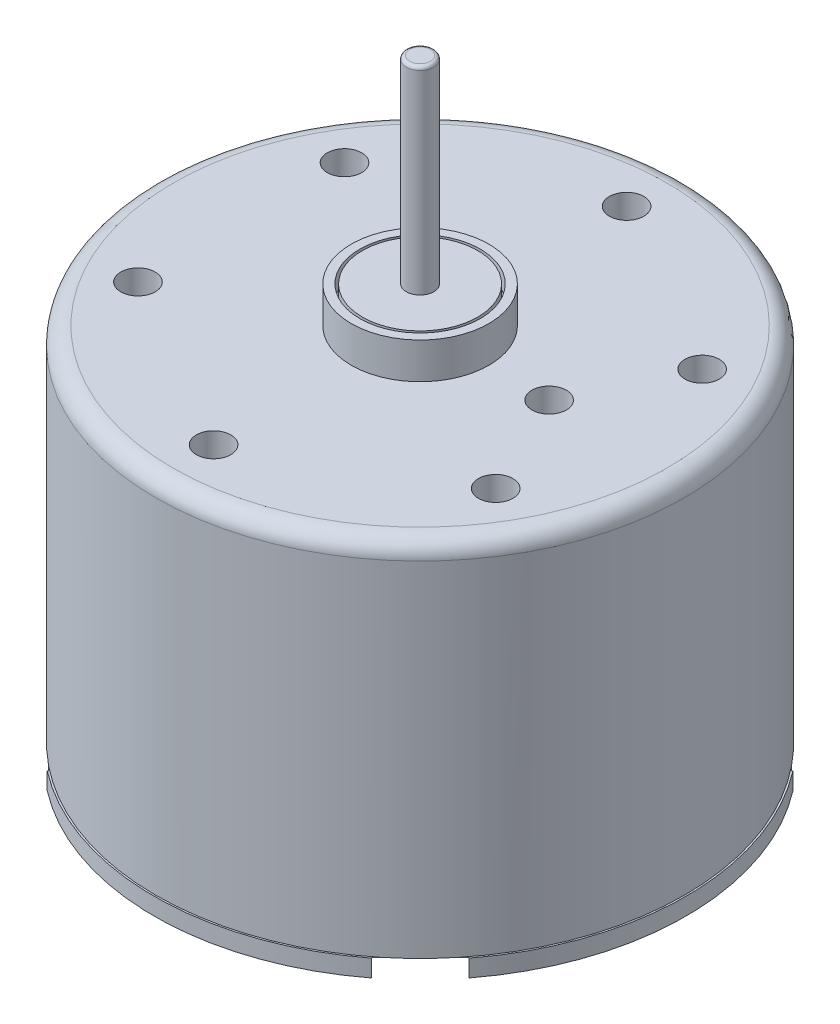
SolidWorks part; units mm, degrees
ref_plane "Plano frontal" through (0, 0, 0) normal (0, 0, 1) x (1, 0, 0)
ref_plane "Plano superior" through (0, 0, 0) normal (0, 1, 0) x (1, 0, 0)
ref_plane "Plano direito" through (0, 0, 0) normal (1, 0, 0) x (0, 0, -1)
sketch "Esboço1" plane through (0, 0, 0) normal (0, 1, 0) x (1, 0, 0)
  circle A0 centre (0, 0) radius 15.35
  dimension "D1" = 30.7
extrude "Ressalto-extrusão1" add sketch "Esboço1" along normal blind 21
sketch "Esboço2" plane through (0, 21, 0) normal (0, 1, 0) x (1, 0, 0)
  circle A0 centre (0, 0) radius 4
  dimension "D1" = 8
extrude "Ressalto-extrusão2" add sketch "Esboço2" along normal blind 2.1
sketch "Esboço3" plane through (0, 23.1, 0) normal (0, 1, 0) x (1, 0, 0)
  circle A0 centre (0, 0) radius 3.35
  circle A1 centre (0, 0) radius 3.5
  dimension "D1" = 6.7
  dimension "D2" = 7
extrude "Corte-extrusão1" cut sketch "Esboço3" against normal blind 1
sketch "Esboço4" plane through (0, 23.1, 0) normal (0, 1, 0) x (1, 0, 0)
  circle A0 centre (0, 0) radius 0.8
  dimension "D1" = 1.6
extrude "Ressalto-extrusão3" add sketch "Esboço4" along normal blind 11.5
fillet "Filete1" radius 0.2 1 edges at (0, 34.6, 0.8)
sketch "Esboço5" plane through (0, 21, 0) normal (0, 1, 0) x (1, 0, 0)
  circle A0 centre (0, 12) radius 1
  circle A1 centre (10.3923, 6) radius 1
  circle A2 centre (10.3923, -6) radius 1
  circle A3 centre (0, -12) radius 1
  circle A4 centre (-10.3923, -6) radius 1
  circle A5 centre (-10.3923, 6) radius 1
  point P16 (0, 0)
  dimension "D1" = 12
  dimension "D2" = 2
  dimension "D3" = 6
extrude "Corte-extrusão2" cut sketch "Esboço5" against normal blind 3
sketch "Esboço6" plane through (0, 21, 0) normal (0, 1, 0) x (1, 0, 0)
  circle A0 centre (7.5, 0) radius 1
  dimension "D1" = 7.5
  dimension "D2" = 2
extrude "Corte-extrusão3" cut sketch "Esboço6" against normal blind 3
fillet "Filete2" radius 1 1 edges at (0, 21, 15.35)
sketch "Esboço7" plane through (0, 0, 0) normal (0, -1, 0) x (1, 0, 0)
  circle A0 centre (0, 0) radius 15.45
  dimension "D1" = 30.9
extrude "Ressalto-extrusão4" add sketch "Esboço7" along normal blind 1
sketch "Esboço8" plane through (0, -1, 0) normal (0, -1, 0) x (1, 0, 0)
  line L0 (-11.2583, 6.5) -> (-5.1962, 3)
  line L1 (0, 13) -> (0, -13) construction
  line L2 (-13, 0) -> (13, 0) construction
  line L3 (11.2583, 6.5) -> (5.1962, 3)
  line L4 (11.2583, -6.5) -> (5.1962, -3)
  line L5 (-11.2583, -6.5) -> (-5.1962, -3)
  arc A0 (-11.2583, -6.5) -> (11.2583, -6.5) centre (0, 0) ccw
  arc A1 (-5.1962, 3) -> (-5.1962, -3) centre (0, 0) ccw
  arc A2 (11.2583, 6.5) -> (-11.2583, 6.5) centre (0, 0) ccw
  arc A3 (5.1962, -3) -> (5.1962, 3) centre (0, 0) ccw
  dimension "D1" = 26
  dimension "D2" = 12
  dimension "D3" = 60
extrude "Corte-extrusão4" cut sketch "Esboço8" against normal blind 1.5
sketch "Esboço9" plane through (0, 0.5, 0) normal (0, -1, 0) x (1, 0, 0)
  circle A0 centre (0, 0) radius 4
  dimension "D1" = 8
extrude "Ressalto-extrusão5" add sketch "Esboço9" along normal blind 2
sketch "Esboço10" plane through (0, 0.5, 0) normal (0, -1, 0) x (1, 0, 0)
  line L0 (-15.45, 0) -> (15.45, 0) construction
  circle A0 centre (-3, 10) radius 3.5
  circle A1 centre (0, 0) radius 15.45 construction
  circle A2 centre (3, -10) radius 3.5
  dimension "D1" = 3
  dimension "D2" = 3
  dimension "D3" = 10
  dimension "D4" = 10
  dimension "D5" = 7
  dimension "D6" = 7
extrude "Corte-extrusão5" cut sketch "Esboço10" against normal blind 3.5 and the other way through all
sketch "Esboço11" plane through (0, 4, 0) normal (0, -1, 0) x (1, 0, 0)
  circle A0 centre (-3, 10) radius 1.25
  circle A1 centre (3, -10) radius 1.25
  circle A3 centre (3, -10) radius 3.5 construction
  dimension "D1" = 2.5
  dimension "D2" = 2.5
  dimension "D3" = 0
  dimension "D4" = 0
extrude "Ressalto-extrusão6" add sketch "Esboço11" along normal blind 4
sketch "Esboço12" plane through (0, -1, 0) normal (0, -1, 0) x (1, 0, 0)
  line L0 (-6.499, -3.0022) -> (-7.1585, -0.0756)
  line L1 (-7.1585, -0.0756) -> (-13.0117, -1.3946)
  line L2 (-13.0117, -1.3946) -> (-12.3522, -4.3212)
  line L3 (-12.3522, -4.3212) -> (-6.499, -3.0022)
  line L4 (0, 0) -> (3.3965, -15.072) construction
  line L5 (13.0117, 1.3946) -> (7.1585, 0.0756)
  line L6 (12.3522, 4.3212) -> (13.0117, 1.3946)
  line L7 (6.499, 3.0022) -> (12.3522, 4.3212)
  line L8 (7.1585, 0.0756) -> (6.499, 3.0022)
  circle A0 centre (0, 0) radius 4 construction
  circle A1 centre (0, 0) radius 15.45 construction
  dimension "D1" = 7
  dimension "D2" = 3
  dimension "D3" = 1.5
  dimension "D4" = 6
extrude "Corte-extrusão6" cut sketch "Esboço12" against normal blind 0.5
sketch "Esboço13" plane through (0, -0.5, 0) normal (0, -1, 0) x (1, 0, 0)
  line L0 (-8.0241, -0.7832) -> (-7.5844, -2.7342)
  line L1 (-8.0241, -0.7832) -> (-8.5119, -0.8931)
  line L2 (-8.5119, -0.8931) -> (-8.0722, -2.8442)
  line L3 (-8.0722, -2.8442) -> (-7.5844, -2.7342)
  line L4 (-7.1585, -0.0756) -> (-13.0117, -1.3946) construction
  line L5 (-12.3522, -4.3212) -> (-6.499, -3.0022) construction
  line L6 (-6.499, -3.0022) -> (-7.1585, -0.0756) construction
  line L7 (0, 0) -> (3.3965, -15.072) construction
  line L8 (8.5119, 0.8931) -> (8.0241, 0.7832)
  line L9 (8.0722, 2.8442) -> (8.5119, 0.8931)
  line L10 (7.5844, 2.7342) -> (8.0722, 2.8442)
  line L11 (7.5844, 2.7342) -> (8.0241, 0.7832)
  circle A0 centre (0, 0) radius 15.45 construction
  dimension "D1" = 0.5
  dimension "D2" = 0.5
  dimension "D3" = 0.5
  dimension "D4" = 1
extrude "Ressalto-extrusão7" add sketch "Esboço13" along normal blind 3
sketch "Esboço15" plane through (-8.2921, 0, -1.8686) normal (-0.9755, 0, -0.2198) x (-0.2198, 0, 0.9755)
  line L0 (1, -3.5) -> (-1, -3.5) construction
  circle A0 centre (0, -2.5) radius 0.5
  dimension "D1" = 1
  dimension "D2" = 1
extrude "Corte-extrusão7" cut sketch "Esboço15" against normal through all
fillet "Filete3" radius 0.25 4 edges at (7.8283, -3.5, 2.7892) (8.268, -3.5, 0.8381) (-8.268, -3.5, -0.8381) (-7.8283, -3.5, -2.7892)
sketch "Esboço16" plane through (0, -1, 0) normal (0, -1, 0) x (1, 0, 0)
  line L0 (0, 0) -> (-10.9477, 10.9477) construction
  line L1 (0, 0) -> (15.45, 0) construction
  line L2 (-12.2702, 9.4418) -> (-10.8187, 7.9903)
  line L3 (-10.8187, 7.9903) -> (-7.9903, 10.8187)
  line L4 (-7.9903, 10.8187) -> (-9.4418, 12.2702)
  line L5 (0, 0) -> (0, 15.45) construction
  line L6 (0, 0) -> (10.9477, 10.9477) construction
  line L7 (7.9903, 10.8187) -> (9.4418, 12.2702)
  line L8 (10.8187, 7.9903) -> (7.9903, 10.8187)
  line L9 (12.2702, 9.4418) -> (10.8187, 7.9903)
  line L10 (0, 0) -> (10.9477, -10.9477) construction
  line L11 (0, 0) -> (-10.9477, -10.9477) construction
  line L12 (12.2702, -9.4418) -> (10.8187, -7.9903)
  line L13 (10.8187, -7.9903) -> (7.9903, -10.8187)
  line L14 (7.9903, -10.8187) -> (9.4418, -12.2702)
  line L15 (-7.9903, -10.8187) -> (-9.4418, -12.2702)
  line L16 (-10.8187, -7.9903) -> (-7.9903, -10.8187)
  line L17 (-12.2702, -9.4418) -> (-10.8187, -7.9903)
  circle A0 centre (0, 0) radius 15.45 construction
  arc A1 (-9.4418, 12.2702) -> (-12.2702, 9.4418) centre (0, 0) ccw
  arc A2 (9.4418, 12.2702) -> (12.2702, 9.4418) centre (0, 0) cw
  arc A3 (9.4418, -12.2702) -> (12.2702, -9.4418) centre (0, 0) ccw
  arc A4 (-9.4418, -12.2702) -> (-12.2702, -9.4418) centre (0, 0) cw
  dimension "D1" = 135
  dimension "D2" = 2
  dimension "D3" = 2
  dimension "D4" = 13.3
extrude "Corte-extrusão8" cut sketch "Esboço16" against normal blind 1
chamfer "Chanfro1" distance 1 angle 63 4 edges at (9.4045, 0, 9.4045) (9.4045, 0, -9.4045) (-9.4045, 0, -9.4045) (-9.4045, 0, 9.4045)
